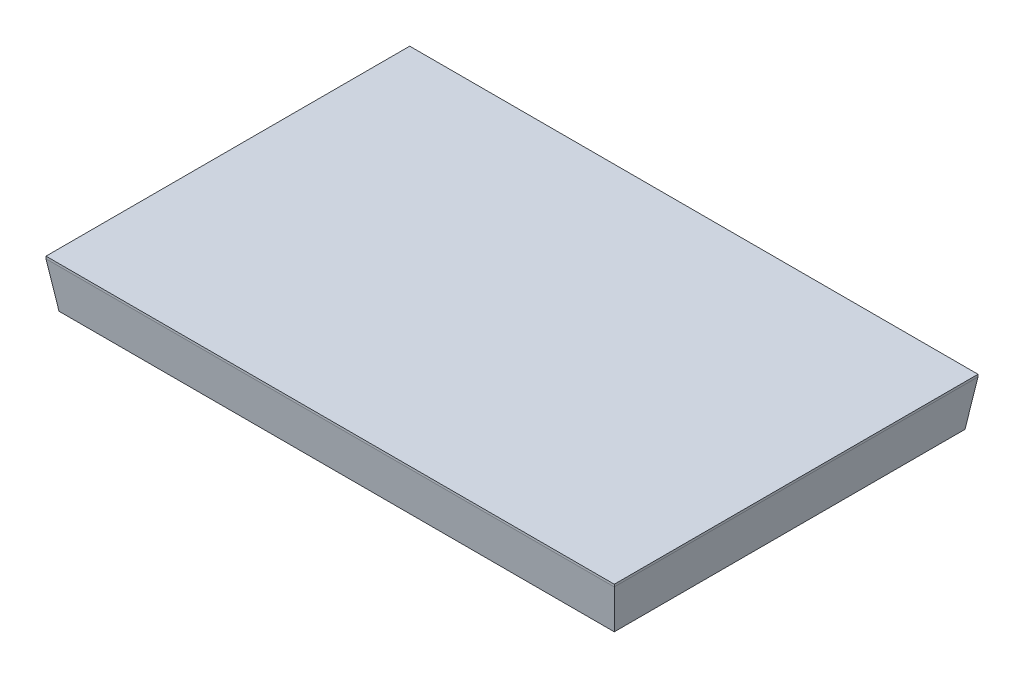
SolidWorks part; units mm, degrees
ref_plane "Front Plane" through (0, 0, 0) normal (0, 0, 1) x (1, 0, 0)
ref_plane "Top Plane" through (0, 0, 0) normal (0, 1, 0) x (1, 0, 0)
ref_plane "Right Plane" through (0, 0, 0) normal (1, 0, 0) x (0, 0, -1)
sketch "Sketch1" plane through (0, 0, 0) normal (0, 1, 0) x (1, 0, 0)
  line L1 (0, 0) -> (558.8, 0)
  line L2 (0, 0) -> (0, 330.2)
  line L3 (0, 330.2) -> (558.8, 330.2)
  line L4 (558.8, 0) -> (558.8, 330.2)
  dimension "D1" = 558.8
  dimension "D2" = 330.2
ref_plane "Plane1" through (0, 266.7, 0) normal (0, 1, 0) x (1, 0, 0)
sketch "Sketch2" plane through (0, 266.7, 0) normal (0, 1, 0) x (1, 0, 0)
  line L0 (0, 330.2) -> (558.8, 330.2) construction
  line L1 (-38.1, -38.1) -> (596.9, -38.1)
  line L2 (-38.1, -38.1) -> (-38.1, 368.3)
  line L3 (-38.1, 368.3) -> (596.9, 368.3)
  line L4 (596.9, -38.1) -> (596.9, 368.3)
  line L5 (0, 165.1) -> (558.8, 165.1) construction
  line L6 (0, 0) -> (0, 330.2) construction
  line L7 (558.8, 0) -> (558.8, 330.2) construction
  point P4 (279.4, 368.3)
  point P7 (279.4, 330.2)
  point P14 (-38.1, 165.1)
  dimension "D1" = 635
  dimension "D2" = 406.4
loft "Loft1" add profiles "Sketch2", "Sketch1" connector at (-38.1, 266.7, -368.3) connector at (0, 0, -330.2)
shell "Shell1" thickness 25.4 removed face at (279.4, 266.7, -165.1)
ref_plane "Plane2" through (0, 215.9, 0) normal (0, 1, 0) x (1, 0, 0)
sketch "Sketch4" plane through (0, 266.7, 0) normal (0, 1, 0) x (1, 0, 0)
  line L1 (-38.1, 368.3) -> (596.9, 368.3)
  line L2 (-38.1, 368.3) -> (-38.1, -38.1)
  line L3 (-38.1, -38.1) -> (596.9, -38.1)
  line L4 (596.9, 368.3) -> (596.9, -38.1)
extrude "Boss-Extrude1" add sketch "Sketch4" along normal blind 2.54
sketch "Sketch5" plane through (0, 215.9, 0) normal (0, 1, 0) x (1, 0, 0)
  line L1 (-180.062, 415.6179) -> (794.0548, 415.6179)
  line L2 (-180.062, 415.6179) -> (-180.062, -79.6836)
  line L3 (-180.062, -79.6836) -> (794.0548, -79.6836)
  line L4 (794.0548, 415.6179) -> (794.0548, -79.6836)
extrude "Cut-Extrude1" cut sketch "Sketch5" against normal up to surface (215.9 mm away) up to face at (279.4, 0, -165.1)
